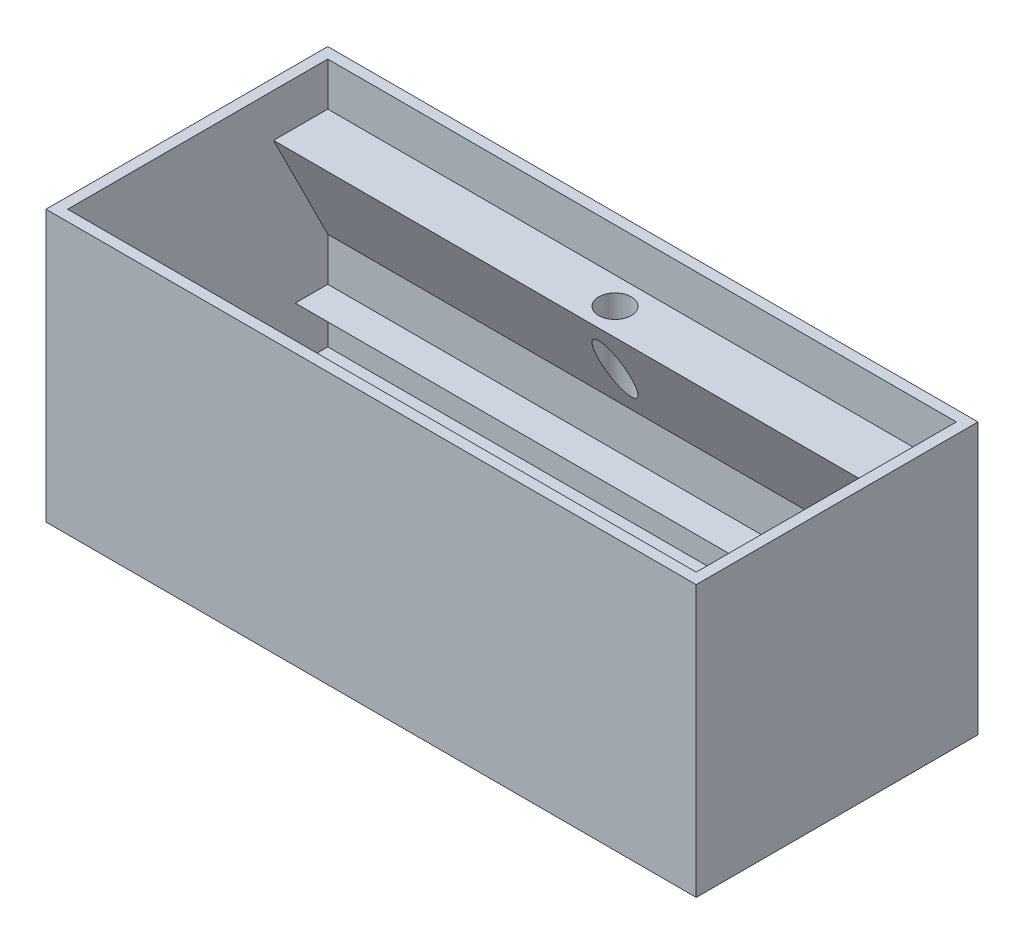
SolidWorks part; units mm, degrees
ref_plane "Front" through (0, 0, 0) normal (0, 0, 1) x (1, 0, 0)
ref_plane "Top" through (0, 0, 0) normal (0, 1, 0) x (1, 0, 0)
ref_plane "Right" through (0, 0, 0) normal (1, 0, 0) x (0, 0, -1)
sketch "Sketch1" plane through (0, 0, 0) normal (0, 1, 0) x (1, 0, 0)
  line L1 (0, 0) -> (60, 0)
  line L2 (0, 0) -> (0, 26)
  line L3 (0, 26) -> (60, 26)
  line L4 (60, 0) -> (60, 26)
  dimension "D1" = 60
  dimension "D2" = 26
extrude "Boss-Extrude1" add sketch "Sketch1" along normal blind 25
sketch "Sketch2" plane through (0, 25, 0) normal (0, 1, 0) x (1, 0, 0)
  line L0 (0, 26) -> (0, 0) construction
  line L1 (1, 25) -> (59, 25)
  line L2 (1, 25) -> (1, 1)
  line L3 (1, 1) -> (59, 1)
  line L4 (59, 25) -> (59, 1)
  line L5 (60, 26) -> (0, 26) construction
  line L6 (60, 0) -> (60, 26) construction
  line L7 (0, 0) -> (60, 0) construction
  dimension "D1" = 1
  dimension "D2" = 1
  dimension "D3" = 1
  dimension "D4" = 1
extrude "Cut-Extrude1" cut sketch "Sketch2" against normal blind 23
sketch "Sketch3" plane through (1, 0, 0) normal (1, 0, 0) x (0, 0, -1)
  line L0 (25, 11) -> (20, 21)
  line L1 (25, 2) -> (25, 25) construction
  line L2 (20, 21) -> (25, 21)
  line L3 (25, 21) -> (25, 11)
  line L4 (0, 25) -> (26, 25) construction
  dimension "D1" = 5
  dimension "D2" = 10
  dimension "D3" = 4
extrude "Boss-Extrude3" add sketch "Sketch3" along normal up to surface (58 mm away) up to face at (59, 13.5, -13)
hole_wizard "Ø1.5 (1.5) Diameter Hole1" positions "Sketch5" profile "Sketch4" hole size "Ø1.5" standard "ANSI Metric" end condition up to next
sketch "Sketch5" plane through (0, 0, 0) normal (0, -1, 0) x (-1, 0, 0)
  line L0 (0, 0) -> (-60, 0) construction
  line L1 (0, 26) -> (0, 0) construction
  point P0 (-6.5, 6.5)
  point P2 (-4.5, 6.5)
  point P4 (-2.5, 6.5)
  dimension "D1" = 6.5
  dimension "D2" = 2.5
  dimension "D3" = 2
  dimension "D4" = 2
sketch "Sketch4" plane through (6.5, 0, -6.5) normal (1, 0, 0) x (0, 0, -1)
  line L0 (0, 0) -> (0, 2)
  line L1 (0, 2) -> (0.75, 2)
  line L2 (0.75, 2) -> (0.75, 0)
  line L5 (0.75, 0) -> (0, 0)
  line L11 (0, -6.35) -> (0, 107.95) construction
  dimension "Thru Hole Dia." = 1.5
  dimension "Thru Hole Depth" = 2
hole_wizard "Ø2.0 (2) Diameter Hole1" positions "Sketch7" profile "Sketch6" hole size "Ø2.0" standard "ANSI Metric" end condition up to next
sketch "Sketch7" plane through (0, 0, 0) normal (0, -1, 0) x (-1, 0, 0)
  line L0 (-60, 0) -> (-60, 26) construction
  line L1 (0, 0) -> (-60, 0) construction
  point P0 (-52, 20)
  dimension "D1" = 8
  dimension "D2" = 20
sketch "Sketch6" plane through (52, 0, -20) normal (1, 0, 0) x (0, 0, -1)
  line L0 (0, 0) -> (0, 2)
  line L1 (0, 2) -> (1, 2)
  line L2 (1, 2) -> (1, 0)
  line L5 (1, 0) -> (0, 0)
  line L11 (0, -6.35) -> (0, 107.95) construction
  dimension "Thru Hole Dia." = 2
  dimension "Thru Hole Depth" = 2
hole_wizard "Ø3.5 (3.5) Diameter Hole1" positions "Sketch9" profile "Sketch8" hole size "Ø3.5" standard "ANSI Metric" end condition up to next
sketch "Sketch9" plane through (0, 0, 0) normal (0, -1, 0) x (-1, 0, 0)
  line L0 (0, 0) -> (-60, 0) construction
  line L1 (-60, 0) -> (-60, 26) construction
  point P0 (-39, 21)
  dimension "D1" = 21
  dimension "D2" = 21
sketch "Sketch8" plane through (39, 0, -21) normal (1, 0, 0) x (0, 0, -1)
  line L0 (0, 0) -> (0, 2)
  line L1 (0, 2) -> (1.75, 2)
  line L2 (1.75, 2) -> (1.75, 0)
  line L5 (1.75, 0) -> (0, 0)
  line L11 (0, -6.35) -> (0, 107.95) construction
  dimension "Thru Hole Dia." = 3.5
  dimension "Thru Hole Depth" = 2
sketch "Sketch10" plane through (1, 0, 0) normal (1, 0, 0) x (0, 0, -1)
  line L0 (25, 4) -> (22, 7)
  line L1 (25, 2) -> (25, 11) construction
  line L2 (22, 7) -> (25, 7)
  line L3 (25, 7) -> (25, 4)
  dimension "D1" = 2
  dimension "D2" = 3
  dimension "D3" = 3
extrude "Boss-Extrude4" add sketch "Sketch10" along normal up to next
hole_wizard "Ø3.0 (3) Diameter Hole1" positions "Sketch12" profile "Sketch11" hole size "Ø3.0" standard "ANSI Metric" end condition up to next
sketch "Sketch12" plane through (0, 21, 0) normal (0, 1, 0) x (1, 0, 0)
  line L0 (59, 25) -> (1, 25) construction
  line L1 (1, 25) -> (1, 20) construction
  point P0 (30, 22.5)
  dimension "D1" = 2.5
  dimension "D2" = 29
sketch "Sketch11" plane through (30, 21, -22.5) normal (1, 0, 0) x (0, 0, 1)
  line L0 (0, 0) -> (0, 5)
  line L1 (0, 5) -> (1.5, 5)
  line L2 (1.5, 5) -> (1.5, 0)
  line L5 (1.5, 0) -> (0, 0)
  line L11 (0, -6.35) -> (0, 107.95) construction
  dimension "Thru Hole Dia." = 3
  dimension "Thru Hole Depth" = 5
